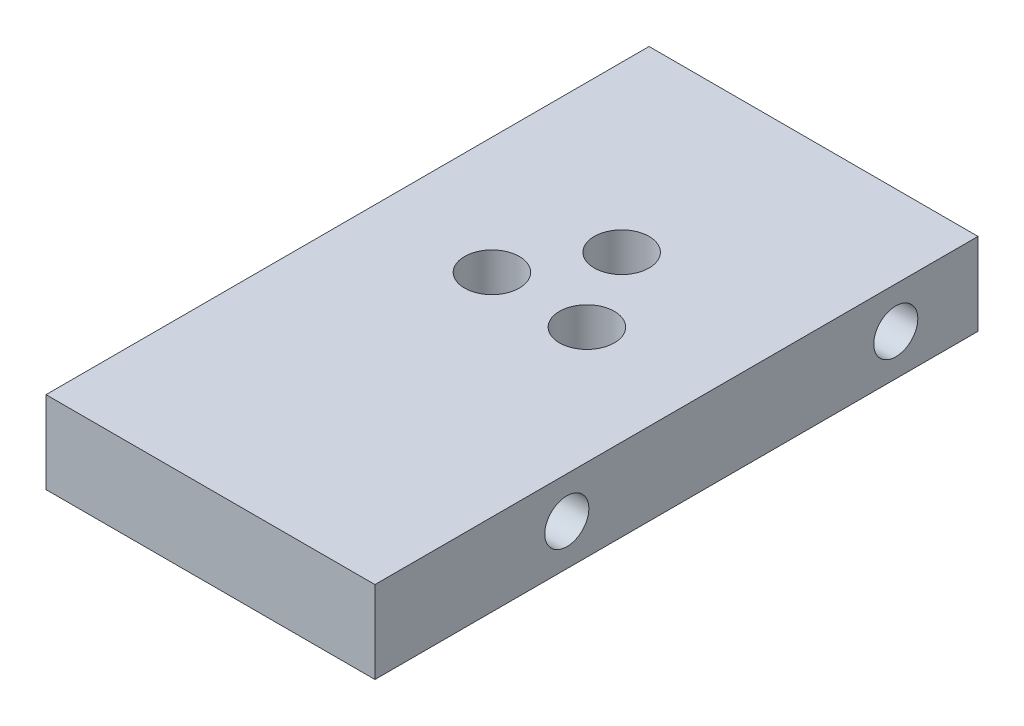
SolidWorks part; units mm, degrees
material "6061 Alloy"
ref_plane "Front Plane" through (0, 0, 0) normal (0, 0, 1) x (1, 0, 0)
ref_plane "Top Plane" through (0, 0, 0) normal (0, 1, 0) x (1, 0, 0)
ref_plane "Right Plane" through (0, 0, 0) normal (1, 0, 0) x (0, 0, -1)
sketch "Sketch1" plane through (0, 0, 0) normal (0, 1, 0) x (1, 0, 0)
  line L1 (-19.05, 34.925) -> (19.05, 34.925)
  line L2 (-19.05, 34.925) -> (-19.05, -34.925)
  line L3 (-19.05, -34.925) -> (19.05, -34.925)
  line L4 (19.05, 34.925) -> (19.05, -34.925)
  line L5 (-19.05, 34.925) -> (19.05, -34.925) construction
  line L6 (-19.05, -34.925) -> (19.05, 34.925) construction
  point P0 (0, 0)
  dimension "D1" = 69.85
  dimension "D2" = 38.1
extrude "Boss-Extrude1" add sketch "Sketch1" along normal blind 9.525
hole_wizard "1/4 (0.25) Diameter Hole1" positions "Sketch3" profile "Sketch2" hole size "1/4" standard "ANSI Inch"
sketch "Sketch3" plane through (0, 0, 0) normal (0, -1, 0) x (-1, 0, 0)
  line L0 (0, 34.925) -> (0, -22.225) construction
  line L1 (-19.05, 34.925) -> (19.05, 34.925) construction
  line L2 (0, 6.35) -> (19.05, 6.35) construction
  line L4 (19.05, 34.925) -> (19.05, -34.925) construction
  circle A0 centre (0, 6.35) radius 6.35
  point P4 (0, 12.7)
  point P21 (5.4993, 3.175)
  point P22 (-5.4993, 3.175)
  dimension "D1" = 57.15
  dimension "D3" = 6.35
  dimension "D2" = 3
sketch "Sketch2" plane through (0, 0, -12.7) normal (1, 0, 0) x (0, 0, -1)
  line L0 (0, 0) -> (0, 18.9257)
  line L1 (0, 18.9257) -> (3.175, 17.018)
  line L2 (3.175, 17.018) -> (3.175, 0)
  line L5 (3.175, 0) -> (0, 0)
  line L10 (0, 18.9257) -> (-3.175, 17.018) construction
  line L11 (0, -6.35) -> (0, 107.95) construction
  dimension "Hole Dia." = 6.35
  dimension "Hole Depth" = 17.018
  dimension "Drill Angle" = 118
hole_wizard "1/4-20 Tapped Hole1" positions "3DSketch1" profile "Sketch4" tap size "1/4-20" standard "ANSI Inch"
sketch3d "3DSketch1"
  line L4 (19.05, 4.7625, -25.4) -> (19.05, 4.7625, -34.925) construction
  line L5 (19.05, 9.525, -34.925) -> (19.05, 0, -34.925) construction
  line L7 (19.05, 4.7625, 12.7) -> (19.05, 4.7625, 22.225) construction
  line L9 (19.05, 9.525, 22.225) -> (19.05, 0, 22.225) construction
  line L10 (19.05, 9.525, 34.925) -> (19.05, 9.525, -34.925) construction
  line L11 (19.05, 0, 34.925) -> (19.05, 0, -34.925) construction
  point P0 (-19.05, 4.7625, -25.4)
  point P2 (-19.05, 4.7625, 12.7)
  point P4 (19.05, 4.7625, 12.7)
  point P6 (19.05, 4.7625, -25.4)
  dimension "D1" = 9.525
  dimension "D2" = 57.15
sketch "Sketch4" plane through (-19.05, 4.7625, -25.4) normal (0, 1, 0) x (0, 0, 1)
  line L0 (0, 0) -> (0, 18.0438)
  line L1 (0, 18.0438) -> (2.5527, 16.51)
  line L2 (2.5527, 16.51) -> (2.5527, 0)
  line L5 (2.5527, 0) -> (0, 0)
  line L10 (0, 18.0438) -> (-2.5527, 16.51) construction
  line L11 (0, -6.35) -> (0, 107.95) construction
  dimension "Tap Drill Dia." = 5.1054
  dimension "Tap Drill Depth" = 16.51
  dimension "Drill Angle" = 118
